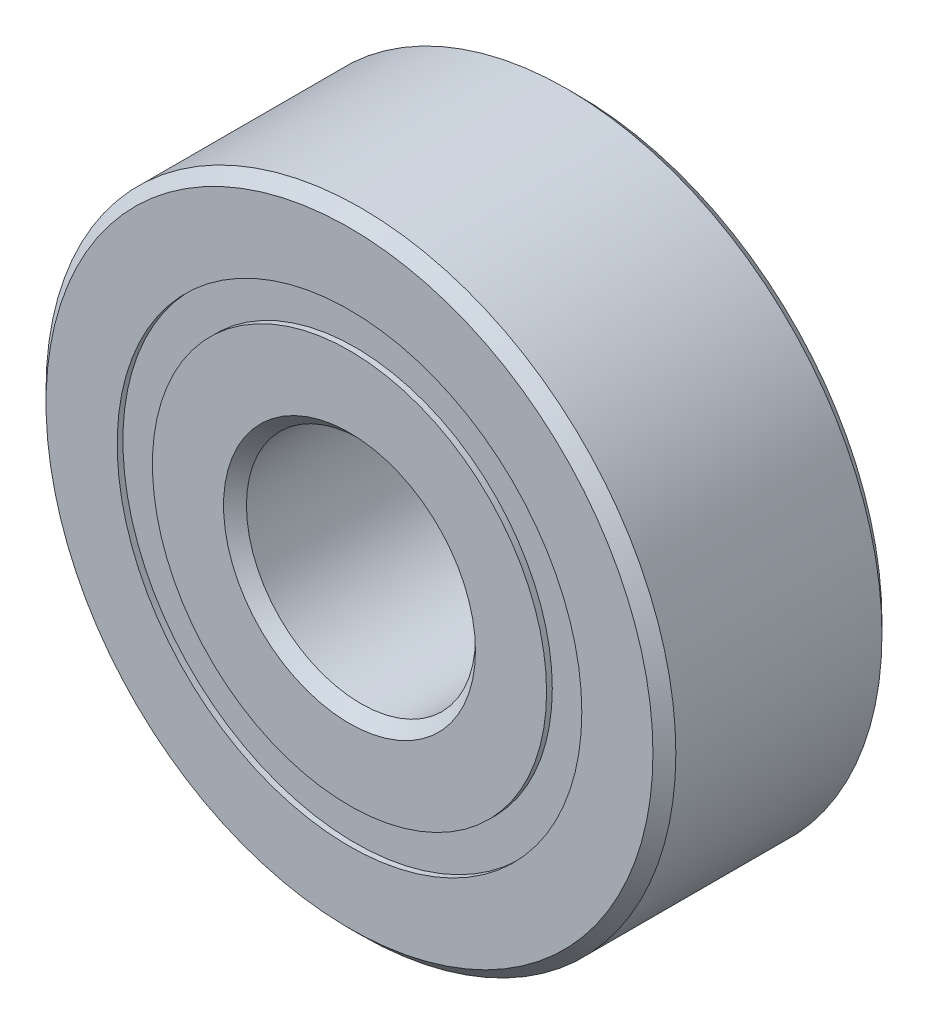
SolidWorks part; units mm, degrees
ref_plane "Front Plane" through (0, 0, 0) normal (0, 0, 1) x (1, 0, 0)
ref_plane "Top Plane" through (0, 0, 0) normal (0, 1, 0) x (1, 0, 0)
ref_plane "Right Plane" through (0, 0, 0) normal (1, 0, 0) x (0, 0, -1)
sketch "Sketch1" plane through (0, 0, 0) normal (1, 0, 0) x (0, 0, -1)
  line L0 (-2, 0) -> (2, 0) construction
  line L1 (0, 5.5) -> (0, -5.5) construction
  line L2 (1.8, 5.5) -> (-1.8, 5.5)
  line L3 (-1.8, 5.5) -> (-2, 5.3)
  line L4 (-2, 5.3) -> (-2, 4.0577)
  line L5 (-2, 4.0577) -> (-0.8889, 4.0577)
  line L6 (2, 4.0577) -> (0.8889, 4.0577)
  line L7 (2, 5.3) -> (2, 4.0577)
  line L8 (1.8, 5.5) -> (2, 5.3)
  line L9 (0, 5.5) -> (0, 3.75) construction
  line L10 (0, 3.75) -> (0, 2) construction
  arc A0 (-0.8889, 4.0577) -> (0.8889, 4.0577) centre (0, 3.75) cw
  point P14 (0, 2)
  dimension "Width" = 4
  dimension "OD" = 11
  dimension "D1" = 45
  dimension "D2" = 0.2
  dimension "Shaft Dia" = 4
  dimension "D3" = 1.7778
  dimension "D4" = 0.3077
revolve "Revolve1" add sketch "Sketch1" angle 360 about L0
sketch "Sketch3" plane through (0, 0, 0) normal (1, 0, 0) x (0, 0, -1)
  line L0 (-2, 3.4423) -> (-0.8889, 3.4423)
  line L1 (0, 5.5) -> (0, -5.5) construction
  line L2 (-2, 5.3) -> (-2, 4.0577) construction
  line L3 (-2, 3.4423) -> (-2, 2.2)
  line L4 (-1.8, 5.5) -> (-2, 5.3) construction
  line L5 (-2, 2.2) -> (-1.8, 2)
  line L6 (-1.8, 2) -> (1.8, 2)
  line L7 (1.8, 5.5) -> (1.8, -5.5) construction
  line L8 (1.8, 2) -> (2, 2.2)
  line L9 (2, -5.3) -> (2, 5.3) construction
  line L10 (2, 2.2) -> (2, 3.4423)
  line L11 (2, 3.4423) -> (0.8889, 3.4423)
  line L13 (1.8, 5.5) -> (2, 5.3) construction
  arc A0 (0.8889, 4.0577) -> (-0.8889, 4.0577) centre (0, 3.75) ccw construction
  arc A1 (0.8889, 3.4423) -> (-0.8889, 3.4423) centre (0, 3.75) cw
revolve "Revolve3" add sketch "Sketch3" angle 360 about L0
sketch "Sketch4" plane through (0, 0, 0) normal (1, 0, 0) x (0, 0, -1)
  line L0 (-0.9406, 3.75) -> (0.9406, 3.75)
  arc A2 (-0.9406, 3.75) -> (0.9406, 3.75) centre (0, 3.75) cw
  arc A3 (0.8889, 4.0577) -> (-0.8889, 4.0577) centre (0, 3.75) ccw construction
revolve "Revolve4" add sketch "Sketch4" angle 360 about L0
ref_axis "Axis1" through (0, 0, -2) along (0, 0, 1)
pattern_circular "CirPattern1" count 12 every 30 about axis through (0, 0, -2) along (0, 0, 1) of bodies 104
sketch "Sketch5" plane through (0, 0, 0) normal (1, 0, 0) x (0, 0, -1)
  line L0 (-2, 4.0577) -> (-0.8889, 4.0577) construction
  line L1 (-1.9, 4.0577) -> (-0.9406, 4.0577)
  line L2 (-1.9, 4.0577) -> (-1.9, 3.4423)
  line L3 (-1.9, 3.4423) -> (-0.9406, 3.4423)
  line L4 (-0.9406, 4.0577) -> (-0.9406, 3.4423)
  line L5 (-2, 3.4423) -> (-0.8889, 3.4423) construction
  line L6 (2, 4.0577) -> (0.8889, 4.0577) construction
  line L7 (1.9, 4.0577) -> (0.9406, 4.0577)
  line L8 (1.9, 4.0577) -> (1.9, 3.4423)
  line L9 (1.9, 3.4423) -> (0.9406, 3.4423)
  line L10 (0.9406, 4.0577) -> (0.9406, 3.4423)
  line L11 (2, 3.4423) -> (0.8889, 3.4423) construction
  line L12 (-1.8, 5.5) -> (-2, 5.3) construction
  point P18 (-1.9, 5.4)
revolve "Revolve5" add sketch "Sketch5" angle 360 about L0
sketch "Sketch6" plane through (0, 0, 0) normal (1, 0, 0) x (0, 0, -1)
  line L0 (2, 0) -> (-2, 0) construction
  line L1 (2, 4.0577) -> (0.9, 4.0577)
  line L2 (2, 4.0577) -> (2, 9.5)
  line L3 (2, 9.5) -> (0.9, 9.5)
  line L4 (0.9, 4.0577) -> (0.9, 9.5)
  dimension "Th" = 1.1
  dimension "Flange OD" = 19
revolve "Revolve6" [suppressed] add sketch "Sketch6" angle 360 about L0
equation "\"D2@Sketch1\" = \"Width@Sketch1\"*.05"
equation "\"D3@Sketch1\" = \"Width@Sketch1\"/2.25"
equation "\"D4@Sketch1\" = (((\"OD@Sketch1\"-\"Width@Sketch1\")/2)/3.25)/3.5"
equation "\"D2@CirPattern1\" = 360/\"Balls@CirPattern1\""
